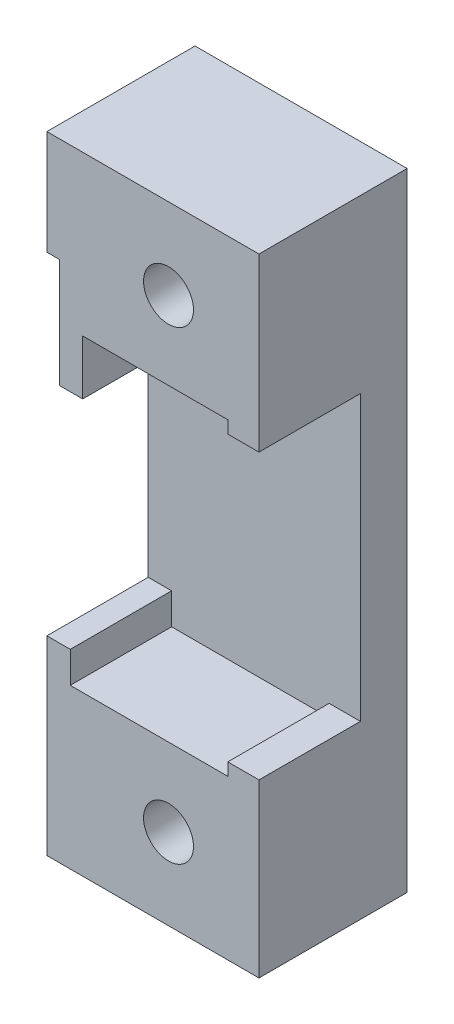
SolidWorks part; units mm, degrees
ref_plane "Front Plane" through (0, 0, 0) normal (1, 0, 0) x (0, 1, 0)
ref_plane "Top Plane" through (0, 0, 0) normal (0, 0, 1) x (0, 1, 0)
ref_plane "Right Plane" through (0, 0, 0) normal (0, 1, 0) x (-1, 0, 0)
sketch "Sketch1" plane through (0, 0, 0) normal (0, 0, 1) x (0, 1, 0)
  line L0 (-9.9, 0) -> (-9.1, 0)
  line L1 (-9.9, 0) -> (-9.9, 10.1)
  line L2 (9.9, 0) -> (9.9, 9.3)
  line L3 (-9.1, 0) -> (-9.1, -2)
  line L4 (9.9, 0) -> (9.1, 0)
  line L5 (9.1, 0) -> (9.1, -2)
  line L6 (9.1, -2) -> (20.1, -2)
  line L7 (20.1, -2) -> (20.1, 11.6)
  line L9 (6.4, 10.8) -> (6.4, 9.3)
  line L10 (6.4, 9.3) -> (9.9, 9.3)
  line L11 (-9.1, -2) -> (-20.1, -2)
  line L12 (-20.1, -2) -> (-20.1, 11.6)
  line L13 (-20.1, 11.6) -> (-7.9, 11.6)
  line L14 (-7.9, 11.6) -> (-7.9, 10.1)
  line L15 (-7.9, 10.1) -> (-9.9, 10.1)
  line L16 (9.1, 0) -> (-9.1, 0) construction
  line L17 (-9.1, -2) -> (9.1, -2)
  line L18 (6.4, 10.8) -> (13.4, 10.8)
  line L19 (13.4, 10.8) -> (13.4, 11.6)
  line L20 (13.4, 11.6) -> (20.1, 11.6)
  line L21 (-20.1, 3.8) -> (-14.9, 3.8) construction
  line L22 (0, 0) -> (0, 3.8) construction
  line L23 (-14.9, 3.8) -> (14.9, 3.8) construction
  line L24 (14.9, 3.8) -> (20.1, 3.8) construction
  line L25 (-7.9, 11.6) -> (13.4, 11.6)
  circle A0 centre (14.9, 3.8) radius 1.6
  circle A1 centre (14.9, 3.8) radius 2.85
  circle A2 centre (-14.9, 3.8) radius 1.6
  circle A3 centre (-14.9, 3.8) radius 2.85
  point P4 (0, 0)
  point P21 (0, 0)
  point P31 (-14.5167, 4.8)
  point P32 (-19.7167, 4.8)
  point P33 (0, 4.5264)
  point P34 (-19.7167, 3.3524)
  point P35 (20.4071, 4.2689)
  point P36 (20.8577, 4)
  point P37 (0, 0)
  point P38 (0, 3.8)
  dimension "D14" = 3.2
  dimension "D15" = 5.7
  dimension "D16" = 3.2
  dimension "D17" = 5.7
  dimension "D1" = 19.8
  dimension "D2" = 10.1
  dimension "D3" = 9.3
  dimension "D4" = 1.5
  dimension "D5" = 1.5
  dimension "D6" = 0.8
  dimension "D7" = 0.8
  dimension "D8" = 2
  dimension "D9" = 2
  dimension "D10" = 7
  dimension "D11" = 40.2
  dimension "D12" = 5.2
  dimension "D13" = 5.2
  dimension "D18" = 2
  dimension "D19" = 3.5
  dimension "D20" = 5.8
extrude "Boss-Extrude1" add sketch "Sketch1" along normal blind 6.5 contours L15 L14 L13 L12 L11 L3 L0 L1 A3 | L20 L19 L18 L9 L10 L2 L4 L5 L6 L7 A1 | A3 A2 | A1 A0 region at (0.1827, -9.5, 0) region at (1, 9.293, 0) region at (-3.8, 12.1306, 0) region at (-3.8, -17.6694, 0)
extrude "Boss-Extrude2" add sketch "Sketch1<3>" against normal blind 3 contours A1 A0 | L20 L19 L18 L9 L10 L2 L4 L5 L6 L7 A1 | L25 L14 L15 L1 L0 L3 L17 L5 L4 L2 L10 L9 L18 L19 | A3 A2 | L15 L14 L13 L12 L11 L3 L0 L1 A3 region at (-4.7646, 0.0634, 0) region at (0.1827, -9.5, 0) region at (1, 9.293, 0) region at (-3.8, 12.1306, 0) region at (-3.8, -17.6694, 0)
sketch "Sketch1<3>" plane through (0, 0, 0) normal (0, 0, 1) x (0, 1, 0) same geometry as "Sketch1"
extrude "Cut-Extrude1" cut sketch "Sketch1<4>" along normal blind 3.5 and the other way through all from surface contours A1 | A3 starting at face at (-4.8, 0, -3)
sketch "Sketch1<4>" plane through (0, 0, 0) normal (0, 0, 1) x (0, 1, 0) same geometry as "Sketch1"
